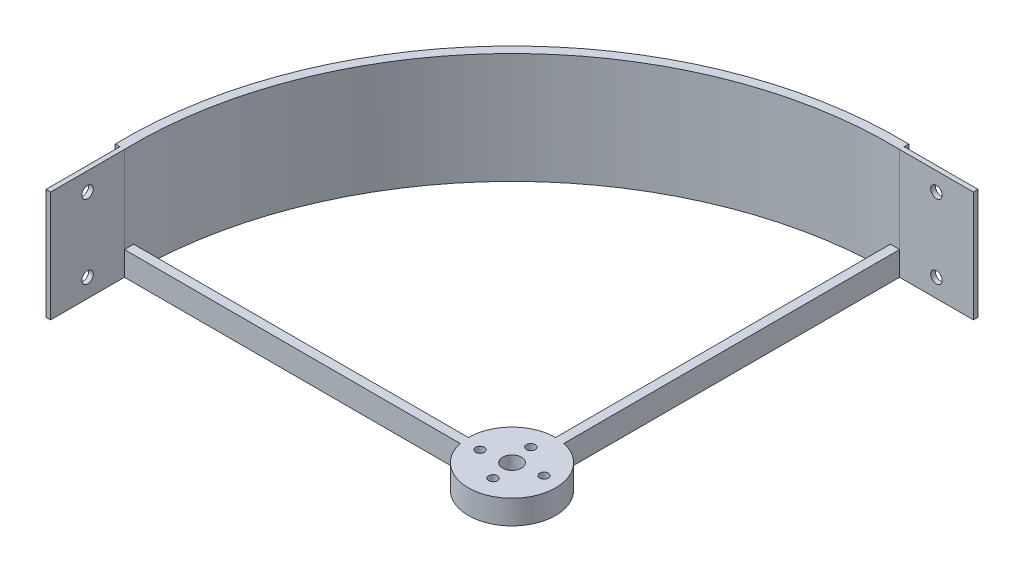
SolidWorks part; units mm, degrees
material "ABS"
ref_plane "Front Plane" through (0, 0, 0) normal (0, 0, 1) x (1, 0, 0)
ref_plane "Top Plane" through (0, 0, 0) normal (0, 1, 0) x (1, 0, 0)
ref_plane "Right Plane" through (0, 0, 0) normal (1, 0, 0) x (0, 0, -1)
sketch "Sketch1" plane through (0, 0, 0) normal (0, 1, 0) x (1, 0, 0)
  line L0 (0, 130.175) -> (0, 9.3426)
  line L1 (3.175, 9.3426) -> (3.175, 130.1363)
  line L2 (0, 0) -> (-22.0351, 22.0351) construction
  line L3 (-22.0351, 22.0351) -> (23.6345, -23.6345) construction
  line L4 (-9.3426, -3.175) -> (-130.1363, -3.175)
  line L5 (-130.175, 0) -> (-9.3426, 0)
  line L6 (3.175, 9.3426) -> (3.175, 130.1363)
  line L7 (3.175, 130.1363) -> (3.175, 133.3122)
  line L8 (-130.1363, -3.175) -> (-133.3122, -3.175)
  circle A0 centre (0, 0) radius 15
  arc A1 (3.175, 130.1363) -> (-130.1363, -3.175) centre (0, 0) ccw
  arc A2 (3.175, 133.3122) -> (-133.3122, -3.175) centre (0, 0) ccw
  dimension "D1" = 30
  dimension "D2" = 133.35
  dimension "D4" = 3.175
  dimension "D3" = 3.175
extrude "Boss-Extrude2" add sketch "Sketch1" along normal blind 8.255 contours A0
extrude "Boss-Extrude3" add sketch "Sketch1<6>" along normal blind 8.255 contours L5 A1 L4 A0 | L6 A1 L0 A0 region at (1.5882, 0, -72.5246) region at (-72.5246, 0, 1.5882)
sketch "Sketch1<6>" plane through (0, 0, 0) normal (0, 1, 0) x (1, 0, 0) same geometry as "Sketch1"
extrude "Boss-Extrude4" add sketch "Sketch1<7>" along normal blind 38.1 contours L7 A2 L8 A1 region at (-93.4129, 0, -93.4129)
sketch "Sketch1<7>" plane through (0, 0, 0) normal (0, 1, 0) x (1, 0, 0) same geometry as "Sketch1"
ref_plane "Plane1" through (-63.4806, 0, -63.4806) normal (0.7071, 0, 0.7071) x (0.7071, 0, -0.7071)
sketch "Sketch5" plane through (0, 8.255, 0) normal (0, 1, 0) x (1, 0, 0)
  line L0 (0, 0) -> (29.635, 0) construction
  line L1 (0, 0) -> (0, 21.5427) construction
  line L2 (0, 130.175) -> (0, 15) construction
  line L3 (0, 0) -> (28.7761, 5.074) construction
  line L4 (21.0363, 3.7093) -> (-27.3456, -4.8218) construction
  line L5 (0, 0) -> (-3.7673, 21.3652) construction
  line L6 (0, 8) -> (0, 0) construction
  line L7 (0, 0) -> (37.8993, -60.1598) construction
  line L8 (0, 0) -> (-19.6346, 0) construction
  line L9 (-130.175, 0) -> (-15, 0) construction
  circle A0 centre (-9.3557, -1.6497) radius 1.5
  circle A1 centre (-1.3892, 7.8785) radius 1.5
  circle A2 centre (1.3892, -7.8785) radius 1.5
  circle A3 centre (9.3557, 1.6497) radius 1.5
  circle A6 centre (0, 0) radius 3.25
  point P18 (0, 0)
  dimension "D3" = 3
  dimension "D7" = 3
  dimension "D8" = 6.5
  dimension "D2" = 8
  dimension "D5" = 80
  dimension "D6" = 8
  dimension "D9" = 90
  dimension "D10" = 9.5
  dimension "D4" = 57.79
extrude "Cut-Extrude3" cut sketch "Sketch5" against normal blind 63.5
sketch "Sketch6" plane through (0, 0, 3.175) normal (0, 0, 1) x (1, 0, 0)
  line L0 (-14.6601, 0) -> (-133.3122, 0) construction
  line L1 (-130.1363, 38.1) -> (-131.7242, 38.1)
  line L2 (-130.1363, 38.1) -> (-130.1363, 0)
  line L3 (-130.1363, 0) -> (-131.7242, 0)
  line L4 (-131.7242, 38.1) -> (-131.7242, 0)
  line L5 (-130.1363, 38.1) -> (-133.3122, 38.1) construction
  point P7 (-131.7242, 38.1)
extrude "Boss-Extrude5" add sketch "Sketch6" along normal blind 25.4
sketch "Sketch7" plane through (3.175, 0, 0) normal (1, 0, 0) x (0, 0, -1)
  line L0 (14.6601, 0) -> (133.3122, 0) construction
  line L1 (130.1363, 38.1) -> (131.7242, 38.1)
  line L2 (130.1363, 38.1) -> (130.1363, 0)
  line L3 (130.1363, 0) -> (131.7242, 0)
  line L4 (131.7242, 38.1) -> (131.7242, 0)
  line L5 (130.1363, 38.1) -> (133.3122, 38.1) construction
  line L6 (130.1363, 38.1) -> (130.1363, 8.255) construction
  point P7 (131.7242, 38.1)
extrude "Boss-Extrude6" add sketch "Sketch7" along normal blind 25.4
sketch "Sketch8" plane through (-131.7242, 0, 0) normal (-1, 0, 0) x (0, 0, 1)
  line L0 (3.175, 19.05) -> (28.575, 19.05) construction
  line L1 (3.175, 38.1) -> (3.175, 0) construction
  line L2 (28.575, 38.1) -> (28.575, 0) construction
  line L3 (15.875, 19.05) -> (15.875, 31.75) construction
  circle A0 centre (15.875, 31.75) radius 1.9844
  circle A1 centre (15.875, 6.35) radius 1.9844
  dimension "D1" = 3.9688
  dimension "D2" = 12.7
extrude "Cut-Extrude4" cut sketch "Sketch8" against normal up to surface (1.588 mm away) up to face at (-130.1363, 16.891, 13.335)
sketch "Sketch9" plane through (0, 0, -131.7242) normal (0, 0, -1) x (-1, 0, 0)
  line L0 (-28.575, 19.05) -> (-3.175, 19.05) construction
  line L1 (-28.575, 0) -> (-28.575, 38.1) construction
  line L2 (-3.175, 0) -> (-3.175, 38.1) construction
  line L3 (-15.875, 19.05) -> (-15.875, 31.75) construction
  circle A0 centre (-15.875, 31.75) radius 1.9844
  circle A1 centre (-15.875, 6.35) radius 1.9844
  dimension "D1" = 3.9688
  dimension "D2" = 12.7
extrude "Cut-Extrude5" cut sketch "Sketch9" against normal up to next
